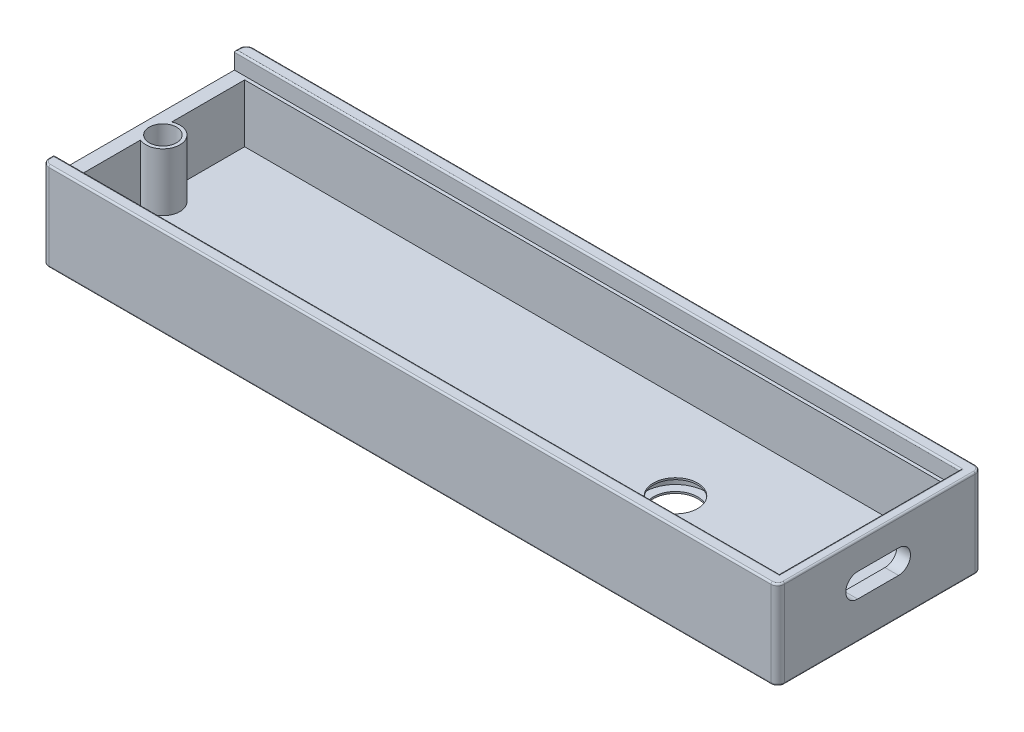
SolidWorks part; units mm, degrees
material "ABS"
ref_plane "Front Plane" through (0, 0, 0) normal (0, 0, 1) x (1, 0, 0)
ref_plane "Top Plane" through (0, 0, 0) normal (0, 1, 0) x (1, 0, 0)
ref_plane "Right Plane" through (0, 0, 0) normal (1, 0, 0) x (0, 0, -1)
sketch "Sketch1" plane through (0, 0, 0) normal (0, 1, 0) x (1, 0, 0)
  line L1 (0, 0) -> (108, 0)
  line L2 (0, 0) -> (0, -30)
  line L3 (0, -30) -> (108, -30)
  line L4 (108, 0) -> (108, -30)
  dimension "D1" = 108
  dimension "D2" = 30
extrude "Boss-Extrude1" add sketch "Sketch1" against normal blind 13
sketch "Sketch2" plane through (0, 0, 0) normal (0, 1, 0) x (1, 0, 0)
  line L0 (0, -30) -> (108, -30) construction
  line L1 (0, -1.75) -> (106.5, -1.75)
  line L2 (0, -1.75) -> (0, -28.25)
  line L3 (0, -28.25) -> (106.5, -28.25)
  line L4 (106.5, -1.75) -> (106.5, -28.25)
  line L6 (108, -30) -> (108, 0) construction
  line L8 (0, 0) -> (0, -30) construction
  line L10 (108, 0) -> (0, 0) construction
  dimension "D1" = 1.75
  dimension "D2" = 1.75
  dimension "D3" = 1.5
extrude "Cut-Extrude1" cut sketch "Sketch2" against normal blind 2.5
sketch "Sketch3" plane through (0, 0, 0) normal (0, 1, 0) x (1, 0, 0)
  line L0 (106.5, -1.75) -> (0, -1.75) construction
  line L1 (2, -2.25) -> (106, -2.25)
  line L2 (2, -2.25) -> (2, -27.75)
  line L3 (2, -27.75) -> (106, -27.75)
  line L4 (106, -2.25) -> (106, -27.75)
  line L5 (106.5, -28.25) -> (106.5, -1.75) construction
  line L6 (0, -28.25) -> (106.5, -28.25) construction
  line L7 (0, -1.75) -> (0, -28.25) construction
  dimension "D1" = 0.5
  dimension "D2" = 0.5
  dimension "D3" = 0.5
  dimension "D4" = 2
extrude "Cut-Extrude2" cut sketch "Sketch3" against normal blind 11
fillet "Fillet1" radius 0.25 12 edges at (0, 0, 0.875) (54, 0, 0) (108, 0, 15) (54, 0, 30) (0, 0, 29.125) (53.25, 0, 28.25) (106.5, 0, 15) (53.25, 0, 1.75) (54, -13, 30) (108, -13, 15) (54, -13, 0) (0, -13, 15)
fillet "Fillet2" radius 1 12 edges at (107.9268, -0.0732, 29.9268) (107.9268, -0.0732, 0.0732) (0.0732, -0.0732, 0.0732) (0.0732, -0.0732, 29.9268) (0, -6.5, 30) (0, -6.5, 0) (108, -6.5, 0) (108, -6.5, 30) (107.9268, -12.9268, 29.9268) (107.9268, -12.9268, 0.0732) (0.0732, -12.9268, 0.0732) (0.0732, -12.9268, 29.9268)
sketch "Sketch4" plane through (0, -11, 0) normal (0, 1, 0) x (1, 0, 0)
  line L0 (0, -1.75) -> (0, -28.25) construction
  line L2 (0, -28.25) -> (106.5, -28.25) construction
  circle A0 centre (3, -15.25) radius 2.5
  dimension "D1" = 5
  dimension "D2" = 3
  dimension "D3" = 13
extrude "Boss-Extrude2" add sketch "Sketch4" along normal up to surface (8.5 mm away) up to face at (54, -2.5, 15)
hole_wizard "Ø2.2 (2.2) Diameter Hole1" positions "3DSketch1" profile "Sketch5" hole size "Ø2.2" standard "ISO"
sketch3d "3DSketch1"
  line L0 (0, -2.5, 1.75) -> (0, -2.5, 28.25) construction
  point P0 (3, -2.5, 15.25)
  dimension "D1" = 3
  dimension "D2" = 13.5
sketch "Sketch5" plane through (3, -2.5, 15.25) normal (1, 0, 0) x (0, 0, 1)
  line L0 (0, 0) -> (0, 7.6609)
  line L1 (0, 7.6609) -> (1.1, 7)
  line L2 (1.1, 7) -> (1.1, 0)
  line L5 (1.1, 0) -> (0, 0)
  line L10 (0, 7.6609) -> (-1.1, 7) construction
  line L11 (0, -6.35) -> (0, 107.95) construction
  dimension "Hole Dia." = 2.2
  dimension "Hole Depth" = 7
  dimension "Drill Angle" = 118
thread "Thread1" pitch 0.4 method cut profile "Thread Profile1" start angle 0, offset 0, length 4, pitch 0.4, diameter 2.2
ref_plane "Plane4" through (1.9, -2.5, 15.25) normal (0, 0, 1) x (-1, 0, 0)
sketch "Thread Profile1" plane through (1.9, -2.5, 15.25) normal (0, 0, 1) x (-1, 0, 0)
  line L0 (0, 0) -> (0, 0.4) construction
  line L1 (0, 0) -> (0.2165, 0.125)
  line L2 (0.2165, 0.125) -> (0.2165, 0.175)
  line L3 (0.2165, 0.175) -> (0, 0.3)
  line L4 (0.2165, 0.15) -> (0, 0.15) construction
  line L11 (0, 0) -> (0, 0.3)
  point P2 (0, 0)
  dimension "Pitch" = 0.4
  dimension "Profile_Angle" = 60
  dimension "Profile_Land" = 0.05
  dimension "Profile_Height" = 0.2165
sketch "Sketch9" plane through (108, 0, 0) normal (1, 0, 0) x (0, 0, -1)
  line L0 (-18.25, -5.75) -> (-12.25, -5.75) construction
  line L1 (-18.25, -4) -> (-12.25, -4)
  line L2 (-18.25, -7.5) -> (-12.25, -7.5)
  line L5 (-30, -12.75) -> (-30, -0.25) construction
  line L6 (-29, -12.75) -> (-1, -12.75) construction
  arc A0 (-18.25, -4) -> (-18.25, -7.5) centre (-18.25, -5.75) ccw
  arc A1 (-12.25, -7.5) -> (-12.25, -4) centre (-12.25, -5.75) ccw
  point P2 (-15.25, -5.75)
  dimension "D1" = 6
  dimension "D2" = 7
  dimension "D3" = 3.5
  dimension "D4" = 14.75
extrude "Cut-Extrude3" cut sketch "Sketch9" against normal up to next
sketch "Sketch10" plane through (0, -13, 0) normal (0, -1, 0) x (1, 0, 0)
  line L0 (107, 29.75) -> (1, 29.75) construction
  line L1 (0.25, 29) -> (0.25, 1) construction
  line L2 (0.25, 14.75) -> (107.75, 14.75) construction
  line L4 (54, 29.25) -> (54, 0) construction
  circle A0 centre (3.25, 26.75) radius 0.75
  circle A1 centre (3.25, 2.75) radius 0.75
  circle A2 centre (104.75, 2.75) radius 0.75
  circle A3 centre (104.75, 26.75) radius 0.75
  dimension "D3" = 1.5
  dimension "D1" = 3
  dimension "D2" = 3
sketch "Sketch11" plane through (106.5, 0, 0) normal (-1, 0, 0) x (0, 0, 1)
  line L0 (28.25, -2.5) -> (28.25, -0.25) construction
  line L1 (1.75, -2.5) -> (28.25, -2.5)
  line L2 (1.75, -2.5) -> (1.75, -1.375)
  line L3 (1.75, -1.375) -> (28.25, -1.375)
  line L4 (28.25, -2.5) -> (28.25, -1.375)
extrude "Cut-Extrude4" cut sketch "Sketch11" against normal blind 1
sketch "Sketch13" plane through (0, -11, 0) normal (0, 1, 0) x (1, 0, 0)
  line L0 (106, -27.75) -> (106, -2.25) construction
  line L2 (1, -30) -> (107, -30) construction
  circle A0 centre (78, -15) radius 3.25
  dimension "D1" = 6.5
  dimension "D2" = 28
  dimension "D3" = 15
extrude "Cut-Extrude5" cut sketch "Sketch13" against normal through all
ref_plane "Plane5" through (0, -12, 0) normal (0, 1, 0) x (1, 0, 0)
sketch "Sketch15" plane through (0, -12, 0) normal (0, 1, 0) x (1, 0, 0)
  circle A0 centre (78, -15) radius 3.5
  dimension "D1" = 7
sketch "Sketch17" plane through (0, -12, 0) normal (0, 1, 0) x (1, 0, 0)
  circle A0 centre (78, -15) radius 4.5
  dimension "D1" = 9
extrude "Cut-Extrude6" cut sketch "Sketch17" against normal mid plane 1.5
sketch "Sketch18" plane through (0, -2.5, 0) normal (0, 1, 0) x (1, 0, 0)
  circle A0 centre (3, -15.25) radius 2
  dimension "D1" = 4
extrude "Cut-Extrude7" cut sketch "Sketch18" against normal blind 4
